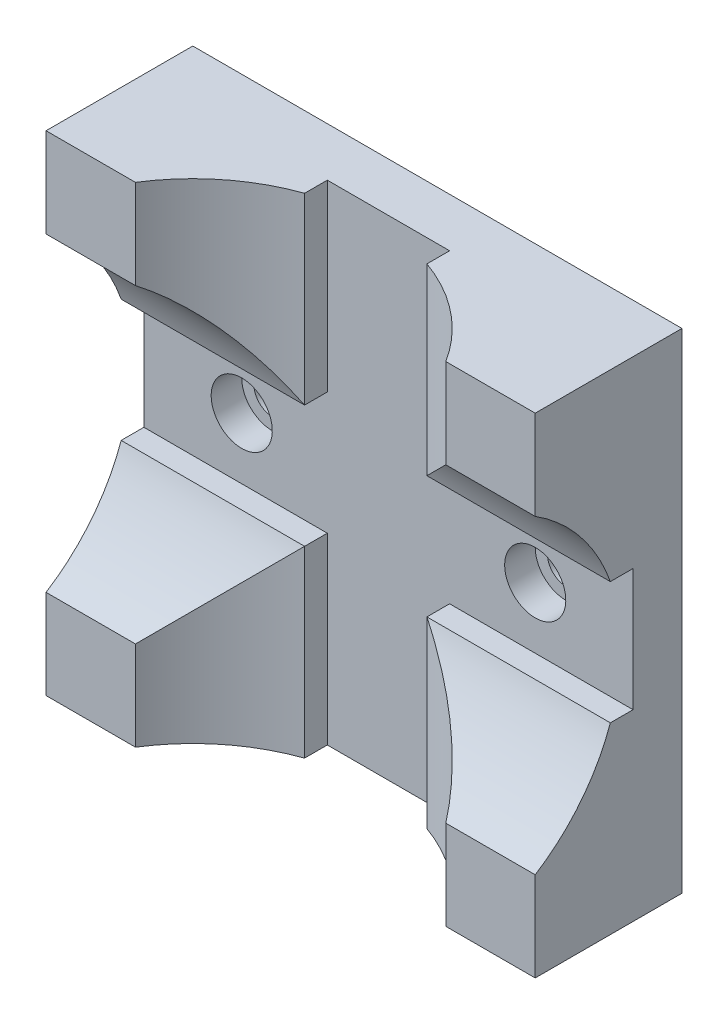
SolidWorks part; units mm, degrees
ref_plane "Front Plane" through (0, 0, 0) normal (0, 0, 1) x (1, 0, 0)
ref_plane "Top Plane" through (0, 0, 0) normal (0, 1, 0) x (1, 0, 0)
ref_plane "Right Plane" through (0, 0, 0) normal (1, 0, 0) x (0, 0, -1)
sketch "Sketch1" plane through (0, 0, 0) normal (0, 0, 1) x (1, 0, 0)
  line L1 (0, 0) -> (40, 0)
  line L2 (0, 0) -> (0, 40)
  line L3 (0, 40) -> (40, 40)
  line L4 (40, 0) -> (40, 40)
  dimension "D1" = 40
  dimension "D2" = 40
extrude "Boss-Extrude1" add sketch "Sketch1" along normal blind 12
ref_plane "Plane1" through (40, 0, 0) normal (1, 0, 0) x (0, 0, -1)
sketch "Sketch2" plane through (40, 0, 0) normal (1, 0, 0) x (0, 0, -1)
  line L0 (-5, 25) -> (-4, 25)
  line L1 (-4, 25) -> (-4, 15)
  line L3 (-5, 15) -> (-5.8579, 15)
  line L5 (-5.8579, 25) -> (-5, 25)
  line L8 (-4, 15) -> (-5, 15)
  arc A0 (-5.8579, 25) -> (-5.8579, 15) centre (-20, 20) ccw
  dimension "D1" = 1
  dimension "D2" = 15
extrude "Cut-Extrude1" cut sketch "Sketch2" against normal blind 40
ref_plane "Plane2" through (0, 0, 0) normal (0, 0, -1) x (-1, 0, 0)
sketch "Sketch3" plane through (0, 0, 0) normal (0, 0, -1) x (-1, 0, 0)
  circle A0 centre (-32, 20) radius 1.5
  circle A1 centre (-8, 20) radius 1.5
  circle A2 centre (-32, 20) radius 2.5
  circle A3 centre (-8, 20) radius 2.5
extrude "Cut-Extrude3" cut sketch "Sketch3" against normal blind 40 contours A2 | A3
extrude "Boss-Extrude3" add sketch "Sketch3<5>" against normal blind 1.5 contours A1 | A0 | A3 | A2
sketch "Sketch3<5>" plane through (0, 0, 0) normal (0, 0, -1) x (-1, 0, 0) same geometry as "Sketch3"
ref_point "Point6"
ref_axis "Axis4" through (20, 20, 4) along (0, 0, 1)
pattern_circular "CirPattern3" count 2 every 90 about axis through (20, 20, 4) along (0, 0, 1) of "Cut-Extrude1"
